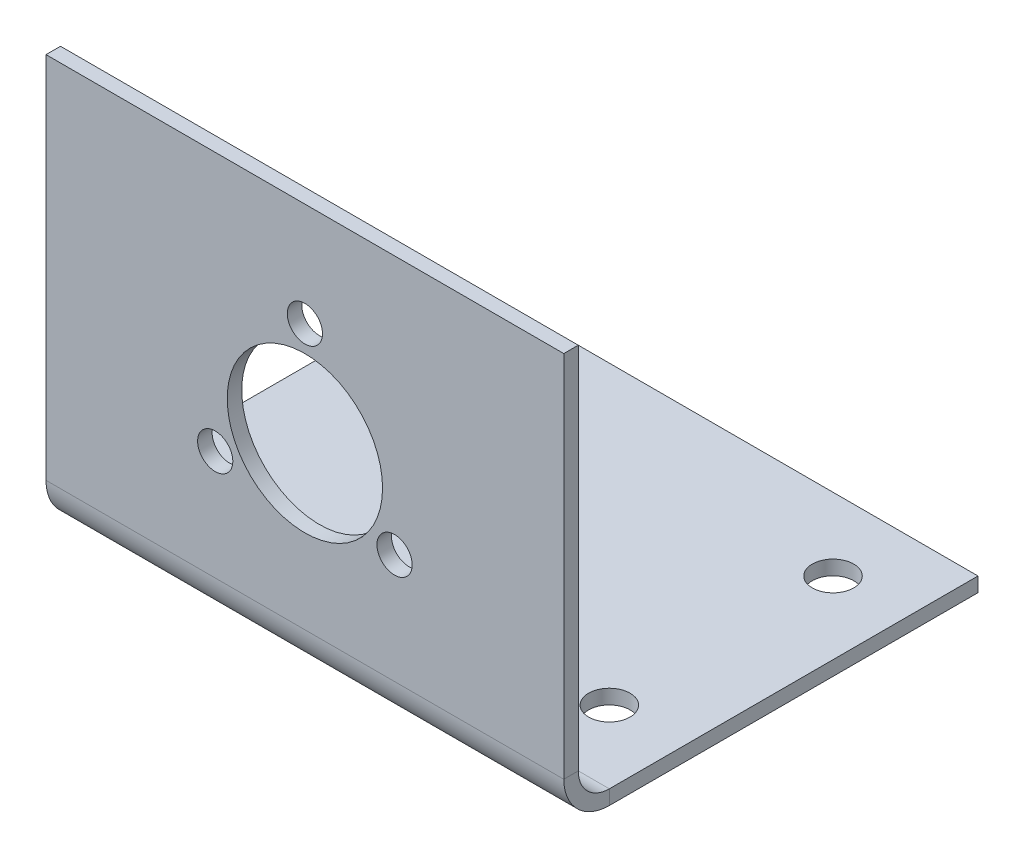
SolidWorks part; units mm, degrees
note: The reader was unsure of these and kept them because the rebuilt part matched: flange length of "Edge-Flange1".
ref_plane "Front Plane" through (0, 0, 0) normal (0, 0, 1) x (1, 0, 0)
ref_plane "Top Plane" through (0, 0, 0) normal (0, 1, 0) x (1, 0, 0)
ref_plane "Right Plane" through (0, 0, 0) normal (1, 0, 0) x (0, 0, -1)
sketch "Sketch6" plane through (0, 0, 0) normal (0, 0, 1) x (1, 0, 0)
  line L1 (0, 0) -> (50, 0)
  line L2 (0, 0) -> (0, 40)
  line L3 (0, 40) -> (50, 40)
  line L4 (50, 0) -> (50, 40)
  dimension "D1" = 50
  dimension "D2" = 40
base flange "Base-Flange2" sketch "Sketch6" thickness 1.4 reverse thickness direction no parameters "D1"=3
sketch "Sketch11" plane through (0, 0, -1.4) normal (0, 0, 1) x (1, 0, 0)
  line L0 (25, 20) -> (16.3397, 15) construction
  line L2 (25, 20) -> (25, 30) construction
  line L4 (25, 20) -> (33.6603, 15) construction
  circle A0 centre (25, 20) radius 7.5
  circle A1 centre (25, 30) radius 1.7
  circle A2 centre (16.3397, 15) radius 1.7
  circle A3 centre (33.6603, 15) radius 1.7
  point P4 (0, 0)
  point P5 (0, 0)
  point P8 (0, 0)
  point P9 (27.5055, 20)
  dimension "D1" = 15
  dimension "D4" = 3.4
  dimension "D2" = 10
extrude "Cut-Extrude2" cut sketch "Sketch11" against normal through all and the other way through all normal cut yes
edge flange "Edge-Flange1" sketch "Sketch34" flange angle 90 flange length 40 flange position material inside bend radius 3 thickness 1.4 relief rectangular parameters "D6"=10
bend "EdgeBend2" bend radius 3 bend angle 90 parameters "D5"=1
sketch "Sketch34" plane through (0, 0, -1.4) normal (0, -1, 0) x (-1, 0, 0)
  line L0 (0, 0) -> (-50, 0) construction
  line L1 (0, 0) -> (-50, 0)
  line L2 (-50, 0) -> (-50, 38.6)
  line L3 (-50, 38.6) -> (0, 38.6)
  line L4 (0, 38.6) -> (0, 0)
sketch "Sketch35" plane through (0, 1.4, 0) normal (0, 1, 0) x (1, 0, 0)
  line L1 (50, 4.4) -> (0, 4.4) construction
  line L2 (50, 40) -> (50, 4.4) construction
  line L3 (0, 4.4) -> (0, 40) construction
  line L4 (0, 40) -> (50, 40) construction
  circle A0 centre (43, 11.4) radius 2
  circle A1 centre (7, 11.4) radius 2
  circle A2 centre (43, 33) radius 2
  circle A3 centre (7, 33) radius 2
  point P8 (0, 0)
  point P9 (0, 0)
  point P10 (0, 0)
  point P11 (0, 0)
  point P12 (44.2707, 11.0121)
  point P13 (44.5217, 33.2726)
  point P20 (0, 0)
  dimension "D4" = 4
  dimension "D5" = 7
  dimension "D1" = 7
  dimension "D2" = 7
  dimension "D3" = 7
extrude "Cut-Extrude3" cut sketch "Sketch35" against normal through all normal cut yes
sketch "Bend-Lines3" [suppressed] plane through (0, 0, 0) normal (0, 1, 0) x (1, 0, 0)
sketch "Bounding-Box3" [suppressed] plane through (0, 0, 0) normal (0, 1, 0) x (1, 0, 0)
sheet metal parameters "Sheet-Metal3" thickness 1.4 parameters "D1"=3
flat pattern "Flat-Pattern3" [suppressed]
sketch "Bend-Lines4" plane through (0, 0, 0) normal (0, 1, 0) x (1, 0, 0)
sketch3d "Bounding-Box4" [suppressed]
  line L0 (0, 0, 0) -> (-50, 0, 0) construction
  line L1 (0, 40, 0) -> (-50, 40, 0) construction
  line L2 (0, 0, 0) -> (0, 40, 0) construction
  line L3 (-50, 0, 0) -> (-50, 40, 0) construction
sheet metal parameters "Sheet-Metal9" thickness 1.4 parameters "D1"=3
flat pattern "Flat-Pattern3"
sketch "Bend-Lines4" plane through (0, 0, 0) normal (0, 0, 1) x (1, 0, 0)
sketch3d "Bounding-Box4" [suppressed]
  line L0 (35, 40, 0) -> (35, 0, 0) construction
  line L1 (0, 40, 0) -> (0, 0, 0) construction
  line L2 (35, 40, 0) -> (0, 40, 0) construction
  line L3 (35, 0, 0) -> (0, 0, 0) construction
sheet metal parameters "Sheet-Metal12" thickness 1.4 parameters "D1"=3
flat pattern "Flat-Pattern3"
sketch "Bend-Lines4" plane through (0, 0, 0) normal (0, 0, 1) x (1, 0, 0)
  line L2 (0, 1.494) -> (50, 1.494) construction
  line L3 (0, 1.494) -> (50, 1.494) construction
  point P0 (50, 38.506)
  point P1 (0, 38.506)
sketch3d "Bounding-Box4" [suppressed]
  line L0 (50, 40, 0) -> (50, -37.0119, 0) construction
  line L1 (0, 40, 0) -> (0, -37.0119, 0) construction
  line L2 (50, 40, 0) -> (0, 40, 0) construction
  line L3 (50, -37.0119, 0) -> (0, -37.0119, 0) construction
bend of the flat pattern "Flatten-<EdgeBend2>1"
sheet metal parameters "Sheet-Metal13" thickness 1.4 parameters "D1"=3
flat pattern "Flat-Pattern3"
sketch "Bend-Lines4" plane through (0, 0, 0) normal (0, 0, 1) x (1, 0, 0)
  line L2 (0, 1.494) -> (50, 1.494) construction
  line L3 (0, 1.494) -> (50, 1.494) construction
sketch3d "Bounding-Box4" [suppressed]
  line L0 (50, 40, 0) -> (50, -37.0119, 0) construction
  line L1 (0, 40, 0) -> (0, -37.0119, 0) construction
  line L2 (50, 40, 0) -> (0, 40, 0) construction
  line L3 (50, -37.0119, 0) -> (0, -37.0119, 0) construction
bend of the flat pattern "Flatten-<EdgeBend2>1"
